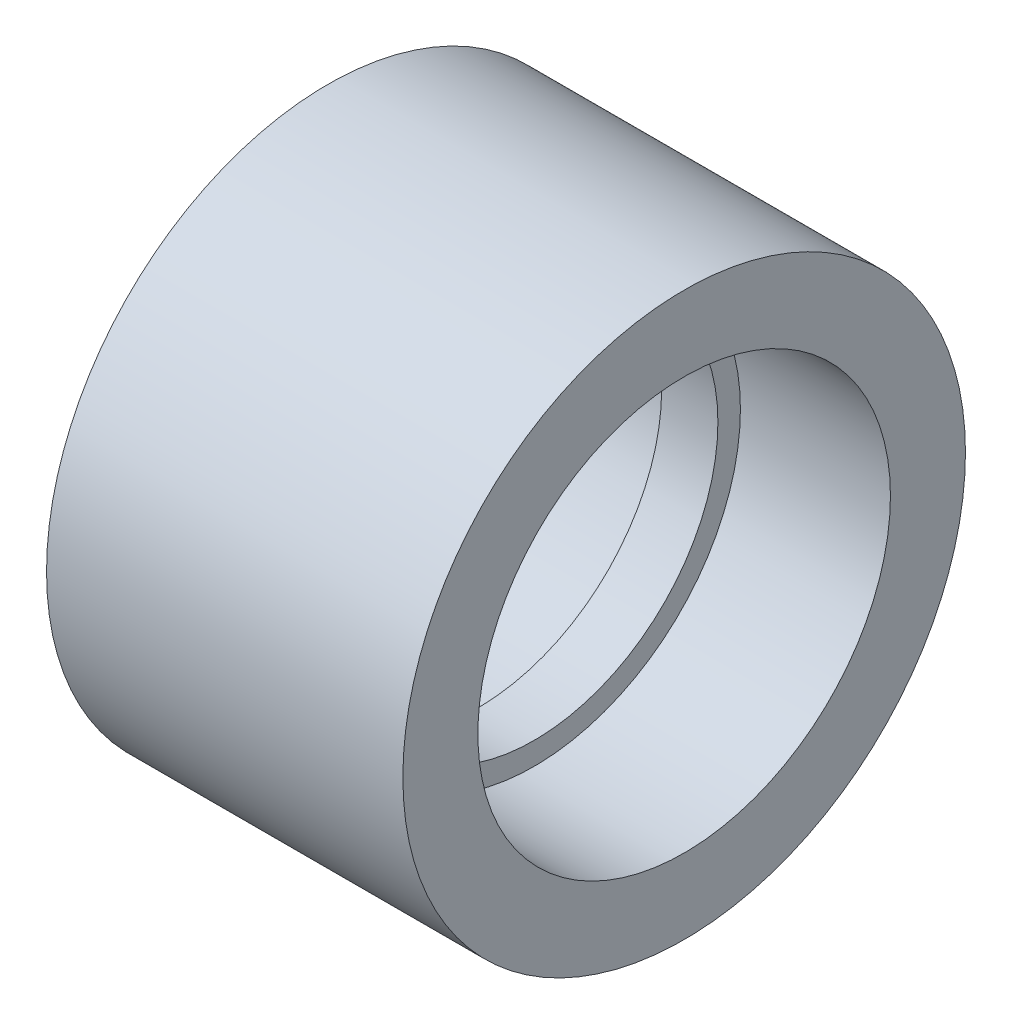
SolidWorks part; units mm, degrees
ref_plane "Front Plane" through (0, 0, 0) normal (0, 0, 1) x (1, 0, 0)
ref_plane "Top Plane" through (0, 0, 0) normal (0, 1, 0) x (1, 0, 0)
ref_plane "Right Plane" through (0, 0, 0) normal (1, 0, 0) x (0, 0, -1)
ref_axis "X-Axis" through (88.99, 0, 0) along (-1, 0, 0)
ref_axis "Y-Axis" through (0, 0, -88.99) along (0, 0, 1)
ref_axis "Z-Axis" through (0, -55, 0) along (0, 1, 0)
sketch "Sketch2" plane through (0, 0, 0) normal (0, 1, 0) x (1, 0, 0)
  line L0 (88.99, 0) -> (-88.99, 0) construction
  line L1 (-9.5, 15) -> (9.5, 15)
  line L2 (-9.5, 15) -> (-9.5, 11)
  line L3 (-9.5, 11) -> (-1.5, 11)
  line L6 (-1.5, 11) -> (-1.5, 9.8)
  line L7 (-1.5, 9.8) -> (1.5, 9.8)
  line L8 (1.5, 11) -> (1.5, 9.8)
  line L9 (0, 88.99) -> (0, -88.99) construction
  line L13 (1.5, 11) -> (9.5, 11)
  line L14 (9.5, 15) -> (9.5, 11)
  point P3 (0, 15)
  dimension "D1" = 11
  dimension "D2" = 1.2
  dimension "D3" = 4
  dimension "D4" = 8
  dimension "D5" = 3
  dimension "D6" = 8
  dimension "D7" = 11
revolve "Revolve1" add sketch "Sketch2" angle 360 about axis through (88.99, 0, 0) along (-1, 0, 0)
sketch "Sketch3" plane through (-9.5, 0, 0) normal (-1, 0, 0) x (0, 0, 1)
  line L0 (-88.99, 0) -> (88.99, 0) construction
  circle A0 centre (10, 0) radius 1.25
  circle A1 centre (0, 0) radius 15 construction
  dimension "D1" = 2.5
  dimension "D2" = 10
